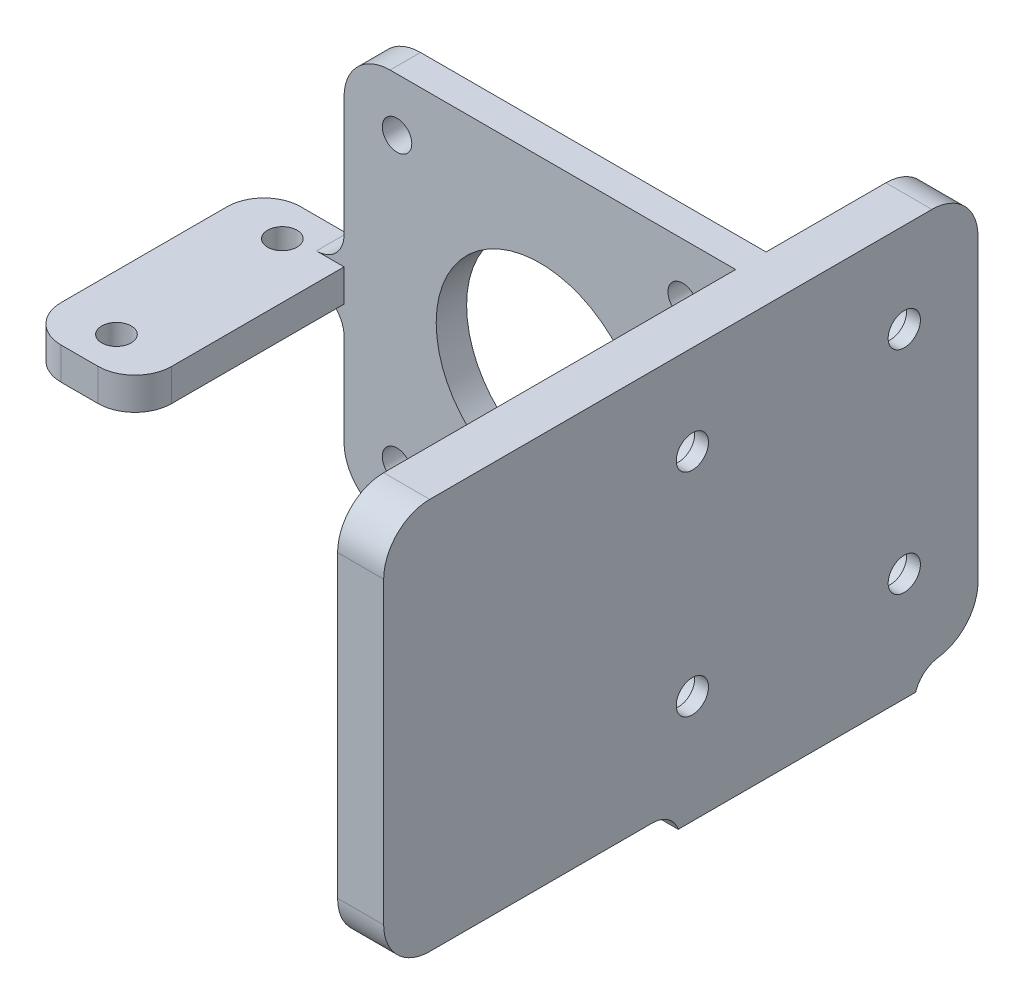
SolidWorks part; units mm, degrees
ref_plane "Alzado" through (0, 0, 0) normal (0, 0, 1) x (1, 0, 0)
ref_plane "Planta" through (0, 0, 0) normal (0, 1, 0) x (1, 0, 0)
ref_plane "Vista lateral" through (0, 0, 0) normal (1, 0, 0) x (0, 0, -1)
sketch "Croquis1" plane through (0, 0, 0) normal (1, 0, 0) x (0, 0, -1)
  line L1 (-23.5797, 14.1196) -> (18.9203, 14.1196)
  line L2 (-23.5797, 14.1196) -> (-23.5797, -28.3804)
  line L3 (-23.5797, -28.3804) -> (18.9203, -28.3804)
  line L4 (18.9203, 14.1196) -> (18.9203, -28.3804)
  dimension "D1" = 42.5
  dimension "D2" = 42.5
extrude "Saliente-Extruir1" add sketch "Croquis1" against normal blind 5
sketch "Croquis6" plane through (0, 0, -18.9203) normal (0, 0, -1) x (-1, 0, 0)
  line L4 (0, 14.1196) -> (0, -28.3804)
  line L5 (0, -28.3804) -> (5, -28.3804)
  line L6 (5, -28.3804) -> (5, 14.1196)
  line L7 (5, 14.1196) -> (0, 14.1196)
  line L8 (0, 14.1196) -> (0, -28.3804)
  line L9 (0, -28.3804) -> (5, -28.3804)
  line L10 (5, -28.3804) -> (5, 14.1196)
  line L11 (5, 14.1196) -> (0, 14.1196)
  dimension "D1" = 0
extrude "Saliente-Extruir2" add sketch "Croquis6" along normal blind 4
sketch "Croquis7" plane through (-5, 0, 0) normal (-1, 0, 0) x (0, 0, 1)
  line L0 (23.5797, -28.3804) -> (-22.9203, -28.3804) construction
  line L1 (-22.9203, 14.1196) -> (-18.9203, 14.1196)
  line L2 (-22.9203, 14.1196) -> (-22.9203, -28.3804)
  line L3 (-22.9203, -28.3804) -> (-18.9203, -28.3804)
  line L4 (-18.9203, 14.1196) -> (-18.9203, -28.3804)
  dimension "D1" = 4
extrude "Saliente-Extruir3" add sketch "Croquis7" along normal blind 42.5
sketch "Croquis8" plane through (0, 0, -18.9203) normal (0, 0, 1) x (1, 0, 0)
  line L0 (-47.5, 14.1196) -> (-41.75, 8.3696) construction
  line L1 (-47.5, -28.3804) -> (-41.75, -22.6304) construction
  line L2 (-40.6186, 7.2382) -> (-11.8814, -21.499) construction
  line L5 (-40.6186, -21.499) -> (-11.8814, 7.2382) construction
  line L7 (-40.6186, -21.499) -> (-11.8814, 7.2382) construction
  line L8 (-40.6186, 7.2382) -> (-11.8814, -21.499) construction
  line L9 (-10.75, 8.3696) -> (-5, 14.1196) construction
  line L10 (-10.75, -22.6304) -> (-5, -28.3804) construction
  circle A0 centre (-26.25, -7.1304) radius 11.25
  circle A1 centre (-41.75, 8.3696) radius 1.6
  circle A2 centre (-10.75, 8.3696) radius 1.6
  circle A3 centre (-10.75, -22.6304) radius 1.6
  circle A4 centre (-41.75, -22.6304) radius 1.6
  dimension "D1" = 22.5
  dimension "D4" = 31
  dimension "D2" = 31
  dimension "D3" = 31
extrude "Cortar-Extruir2" cut sketch "Croquis8" against normal blind 4
sketch "Croquis10" plane through (-47.5, 0, 0) normal (-1, 0, 0) x (0, 0, 1)
  line L0 (-18.9203, -28.3804) -> (-18.9203, 14.1196) construction
  line L1 (-22.9203, -28.3804) -> (-18.9203, -28.3804)
  line L3 (-22.9203, -8.3804) -> (-18.9203, -8.3804)
  line L4 (-22.9203, -8.3804) -> (-18.9203, -8.3804)
  line L5 (-22.9203, -8.3804) -> (-22.9203, -4.8804)
  line L6 (-22.9203, -4.8804) -> (-18.9203, -4.8804)
  line L7 (-18.9203, -8.3804) -> (-18.9203, -4.8804)
  line M3 (-22.9203, 14.1196) -> (-22.9203, -28.3804)
  line M5 (-18.9203, -28.3804) -> (-18.9203, 14.1196)
  dimension "D1" = 20
  dimension "D2" = 3.5
extrude "Saliente-Extruir4" add sketch "Croquis10" along normal blind 12 contours L6 L3 M3 M5
sketch "Croquis11" plane through (0, 0, -18.9203) normal (0, 0, 1) x (1, 0, 0)
  line L1 (-59.5, -4.8804) -> (-47.5, -4.8804)
  line L2 (-59.5, -4.8804) -> (-59.5, -8.3804)
  line L3 (-59.5, -8.3804) -> (-47.5, -8.3804)
  line L4 (-47.5, -4.8804) -> (-47.5, -8.3804)
extrude "Saliente-Extruir5" add sketch "Croquis11" along normal blind 22
sketch "Croquis12" plane through (0, -4.8804, 0) normal (0, 1, 0) x (1, 0, 0)
  line L0 (-59.5, 22.9203) -> (-47.5, -3.0797) construction
  line L1 (-59.5, -3.0797) -> (-47.5, 22.9203) construction
  circle A0 centre (-53.5, 18.9203) radius 1.6
  circle A1 centre (-53.5, 0.9203) radius 1.6
  point P11 (-53.5, 9.9203)
  dimension "D1" = 18
extrude "Cortar-Extruir4" cut sketch "Croquis12" against normal blind 3.5
fillet "Redondeo1" radius 5 2 edges at (-2.5, -28.3804, 23.5797) (-2.5, 14.1196, 23.5797)
fillet "Redondeo2" radius 5 2 edges at (-47.5, -28.3804, -20.9203) (-47.5, 14.1196, -20.9203)
fillet "Redondeo3" radius 4 3 edges at (-59.5, -6.6304, -22.9203) (-59.5, -6.6304, 3.0797) (-47.5, -6.6304, 3.0797)
sketch "Croquis13" plane through (0, 0, -18.9203) normal (0, 0, 1) x (1, 0, 0)
  line L7 (-47.5, -8.3804) -> (-47.5, -23.3804)
  line L8 (-42.5, -28.3804) -> (-5, -28.3804)
  line L9 (-5, -28.3804) -> (-5, 14.1196)
  line L10 (-5, 14.1196) -> (-42.5, 14.1196)
  line L11 (-47.5, 9.1196) -> (-47.5, -4.8804)
  line L13 (-47.5, -4.8804) -> (-47.5, -8.3804)
  line L14 (-47.5, -8.3804) -> (-47.5, -23.3804)
  line L15 (-42.5, -28.3804) -> (-5, -28.3804)
  line L16 (-5, -28.3804) -> (-5, 14.1196)
  line L17 (-5, 14.1196) -> (-42.5, 14.1196)
  line L18 (-47.5, 9.1196) -> (-47.5, -4.8804)
  line L20 (-47.5, -4.8804) -> (-47.5, -8.3804)
  arc A3 (-47.5, -23.3804) -> (-42.5, -28.3804) centre (-42.5, -23.3804) ccw
  arc A4 (-42.5, 14.1196) -> (-47.5, 9.1196) centre (-42.5, 9.1196) ccw
  arc A6 (-47.5, -23.3804) -> (-42.5, -28.3804) centre (-42.5, -23.3804) ccw
  arc A7 (-42.5, 14.1196) -> (-47.5, 9.1196) centre (-42.5, 9.1196) ccw
  dimension "D1" = 0
extrude "Cortar-Extruir5" cut sketch "Croquis13" against normal blind 0.7
sketch "Croquis14" plane through (0, 0, -22.9203) normal (0, 0, -1) x (-1, 0, 0)
  line L0 (0, -28.3804) -> (42.5, -28.3804) construction
  line L1 (0, 14.1196) -> (5, 14.1196)
  line L2 (0, 14.1196) -> (0, -28.3804)
  line L3 (0, -28.3804) -> (5, -28.3804)
  line L4 (5, 14.1196) -> (5, -28.3804)
  dimension "D1" = 5
extrude "Saliente-Extruir6" add sketch "Croquis14" along normal blind 18
sketch "Croquis15" plane through (0, 0, 0) normal (1, 0, 0) x (0, 0, -1)
  circle A0 centre (9.9203, 4.3696) radius 1.75
  circle A1 centre (32.9203, 4.3696) radius 1.75
  circle A2 centre (32.9203, -18.6304) radius 1.75
  circle A3 centre (9.9203, -18.6304) radius 1.75
  dimension "D1" = 23
  dimension "D2" = 23
extrude "Cortar-Extruir6" cut sketch "Croquis15" against normal blind 5
sketch "Croquis16" plane through (-5, 0, 0) normal (-1, 0, 0) x (0, 0, 1)
  circle A4 centre (-9.9203, 4.3696) radius 2.8
  circle A5 centre (-9.9203, -18.6304) radius 2.8
extrude "Cortar-Extruir7" cut sketch "Croquis16" against normal blind 3.5
sketch "Croquis17" plane through (-5, 0, 0) normal (-1, 0, 0) x (0, 0, 1)
  circle A4 centre (-32.9203, 4.3696) radius 2.8
  circle A5 centre (-32.9203, -18.6304) radius 2.8
extrude "Cortar-Extruir8" cut sketch "Croquis17" against normal blind 3.5
fillet "Redondeo5" radius 5 2 edges at (-2.5, -28.3804, -40.9203) (-2.5, 14.1196, -40.9203)
sketch "Croquis18" plane through (0, -8.3804, 0) normal (0, -1, 0) x (1, 0, 0)
  line L5 (-59.5, -0.9203) -> (-59.5, -18.9203)
  line L6 (-55.5, -22.9203) -> (-47.5, -22.9203)
  line L7 (-47.5, -22.9203) -> (-47.5, -19.6203)
  line L8 (-47.5, -19.6203) -> (-47.5, -0.9203)
  line L9 (-51.5, 3.0797) -> (-55.5, 3.0797)
  line L10 (-59.5, -0.9203) -> (-59.5, -18.9203)
  line L11 (-55.5, -22.9203) -> (-47.5, -22.9203)
  line L12 (-47.5, -22.9203) -> (-47.5, -19.6203)
  line L13 (-47.5, -19.6203) -> (-47.5, -0.9203)
  line L14 (-51.5, 3.0797) -> (-55.5, 3.0797)
  circle A0 centre (-53.5, -0.9203) radius 1.6 construction
  circle A1 centre (-53.5, -18.9203) radius 1.6 construction
  circle A2 centre (-53.5, -0.9203) radius 1.6
  arc A3 (-59.5, -18.9203) -> (-55.5, -22.9203) centre (-55.5, -18.9203) ccw
  arc A4 (-47.5, -0.9203) -> (-51.5, 3.0797) centre (-51.5, -0.9203) ccw
  arc A5 (-55.5, 3.0797) -> (-59.5, -0.9203) centre (-55.5, -0.9203) ccw
  arc A6 (-59.5, -18.9203) -> (-55.5, -22.9203) centre (-55.5, -18.9203) ccw
  arc A7 (-47.5, -0.9203) -> (-51.5, 3.0797) centre (-51.5, -0.9203) ccw
  arc A8 (-55.5, 3.0797) -> (-59.5, -0.9203) centre (-55.5, -0.9203) ccw
  circle A9 centre (-53.5, -18.9203) radius 1.6
  dimension "D1" = 0
extrude "Saliente-Extruir8" add sketch "Croquis18" along normal blind 2
sketch "Croquis19" plane through (0, -4.8804, 0) normal (0, 1, 0) x (1, 0, 0)
  line L0 (-51.5, -3.0797) -> (-55.5, -3.0797) construction
  line L1 (-59.5, 18.9203) -> (-59.5, 0.9203) construction
  line L2 (-55.5, 22.9203) -> (-47.5, 22.9203) construction
  line L3 (-47.5, 22.9203) -> (-47.5, 19.6203) construction
  line L4 (-47.5, 0.9203) -> (-47.5, 19.6203) construction
  line L5 (-51.5, -3.0797) -> (-55.5, -3.0797)
  line L6 (-59.5, 18.9203) -> (-59.5, 0.9203)
  line L7 (-55.5, 22.9203) -> (-47.5, 22.9203)
  line L8 (-47.5, 22.9203) -> (-47.5, 19.6203)
  line L9 (-47.5, 0.9203) -> (-47.5, 19.6203)
  arc A0 (-51.5, -3.0797) -> (-47.5, 0.9203) centre (-51.5, 0.9203) ccw construction
  arc A1 (-59.5, 0.9203) -> (-55.5, -3.0797) centre (-55.5, 0.9203) ccw construction
  arc A2 (-55.5, 22.9203) -> (-59.5, 18.9203) centre (-55.5, 18.9203) ccw construction
  circle A3 centre (-53.5, 18.9203) radius 1.6 construction
  circle A4 centre (-53.5, 0.9203) radius 1.6 construction
  arc A5 (-51.5, -3.0797) -> (-47.5, 0.9203) centre (-51.5, 0.9203) ccw
  arc A6 (-59.5, 0.9203) -> (-55.5, -3.0797) centre (-55.5, 0.9203) ccw
  arc A7 (-55.5, 22.9203) -> (-59.5, 18.9203) centre (-55.5, 18.9203) ccw
  circle A8 centre (-53.5, 18.9203) radius 1.6
  circle A9 centre (-53.5, 0.9203) radius 1.6
extrude "Cortar-Extruir9" cut sketch "Croquis19" against normal blind 2
fillet "Redondeo7" radius 3 1 edges at (-47.5, -6.8804, -21.2703)
fillet "Redondeo8" radius 3 1 edges at (-47.5, -10.3804, -21.2703)
sketch "Croquis20" plane through (0, -28.3804, 0) normal (0, -1, 0) x (1, 0, 0)
  line L8 (-5, -22.9203) -> (-5, -35.9203)
  line L9 (-5, -35.9203) -> (0, -35.9203)
  line L10 (0, -35.9203) -> (0, 18.5797)
  line L11 (0, 18.5797) -> (-5, 18.5797)
  line L12 (-5, 18.5797) -> (-5, -19.6203)
  line L13 (-5, -19.6203) -> (-42.5, -19.6203)
  line L14 (-42.5, -19.6203) -> (-42.5, -22.9203)
  line L15 (-42.5, -22.9203) -> (-5, -22.9203)
  line L16 (-5, -22.9203) -> (-5, -35.9203)
  line L17 (-5, -35.9203) -> (0, -35.9203)
  line L18 (0, -35.9203) -> (0, 18.5797)
  line L19 (0, 18.5797) -> (-5, 18.5797)
  line L20 (-5, 18.5797) -> (-5, -19.6203)
  line L21 (-5, -19.6203) -> (-42.5, -19.6203)
  line L22 (-42.5, -19.6203) -> (-42.5, -22.9203)
  line L23 (-42.5, -22.9203) -> (-5, -22.9203)
  dimension "D1" = 0
extrude "Saliente-Extruir9" add sketch "Croquis20" along normal blind 2
sketch "Croquis21" plane through (0, -30.3804, 0) normal (0, -1, 0) x (1, 0, 0)
  line L0 (-42.5, -22.9203) -> (-5, -22.9203) construction
  line L9 (-5, -35.9203) -> (-5, -22.9203)
  line L10 (-5, -22.9203) -> (-16.2298, -22.9203)
  line L11 (-5, 18.5797) -> (-5, -19.6203) construction
  line L12 (-5, -19.6203) -> (-42.5, -19.6203) construction
  line L13 (-5, -19.6203) -> (-16.2298, -19.6203)
  line L14 (-5, -19.6203) -> (-5, -4.3631)
  arc A0 (-5, -35.9203) -> (-16.2298, -22.9203) centre (-17.1149, -35.0352) ccw
  arc A1 (-5, -4.3631) -> (-16.2298, -19.6203) centre (-18.2435, -6.3768) cw
  line M9 (-42.5, -22.9203) -> (-5, -22.9203)
  line M10 (-5, -22.9203) -> (-5, -35.9203)
  line M15 (-5, -19.6203) -> (-42.5, -19.6203)
extrude "Saliente-Extruir10" add sketch "Croquis21" against normal blind 2 contours L14 A1 M15 | A0 M10 M9
sketch "Croquis22" plane through (-5, 0, 0) normal (-1, 0, 0) x (0, 0, 1)
  line L1 (-8.3905, -30.3804) -> (18.5797, -30.3804)
  line L2 (-8.3905, -30.3804) -> (-8.3905, -28.3804)
  line L3 (-8.3905, -28.3804) -> (18.5797, -28.3804)
  line L4 (18.5797, -30.3804) -> (18.5797, -28.3804)
extrude "Cortar-Extruir10" cut sketch "Croquis22" against normal blind 5
sketch "Croquis23" plane through (-5, 0, 0) normal (-1, 0, 0) x (0, 0, 1)
  line L1 (-35.9203, -28.3804) -> (-34.1501, -28.3804)
  line L2 (-35.9203, -28.3804) -> (-35.9203, -30.3804)
  line L3 (-35.9203, -30.3804) -> (-34.1501, -30.3804)
  line L4 (-34.1501, -28.3804) -> (-34.1501, -30.3804)
extrude "Cortar-Extruir11" cut sketch "Croquis23" against normal blind 5
fillet "Redondeo9" radius 3 2 edges at (-2.5, -28.3804, -34.1501) (-2.5, -28.3804, -8.3905)
